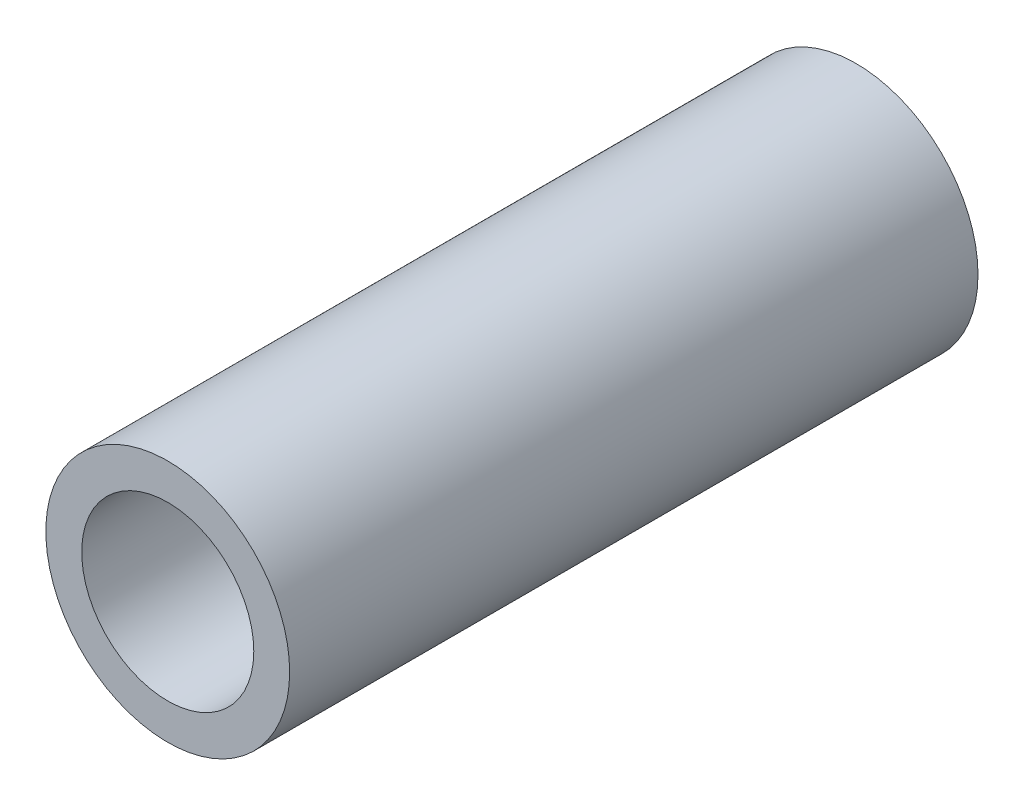
SolidWorks part; units mm, degrees
material "Silicon Rubber"
ref_plane "X-Y Datum" through (0, 0, 0) normal (0, 0, 1) x (1, 0, 0)
ref_plane "X-Z Datum" through (0, 0, 0) normal (0, 1, 0) x (1, 0, 0)
ref_plane "Y-Z Datum" through (0, 0, 0) normal (1, 0, 0) x (0, 0, -1)
sketch3d "3DSketch1"
  line L0 (0, 0, 0) -> (0, 0, 76.2)
  dimension "D1" = 76.2
sweep "Sweep1" add path "3DSketch1" circular profile diameter 26.9875 parameters "D3"=26.9875
sweep "Cut-Sweep1" cut path "3DSketch1<2>" circular profile diameter 19.05 parameters "D3"=19.05
sketch3d "3DSketch1<2>" same geometry as "3DSketch1"
sketch3d "3DSketch2"
  circle A0 centre (0, 0, 50.8) radius 9.525 construction
  circle A1 centre (0, 0, 25.4) radius 9.525 construction
  circle A2 centre (0, 0, 76.2) radius 9.525 construction
  point P1 (-34.0496, -7.516, 93.9649)
  point P4 (0, 0, 15.875)
  point P6 (0, 0, 66.675)
  point P7 (0, 0, 59.189)
  point P10 (0, 0, 41.275)
  dimension "D1" = 25.4
  dimension "D2" = 25.4
